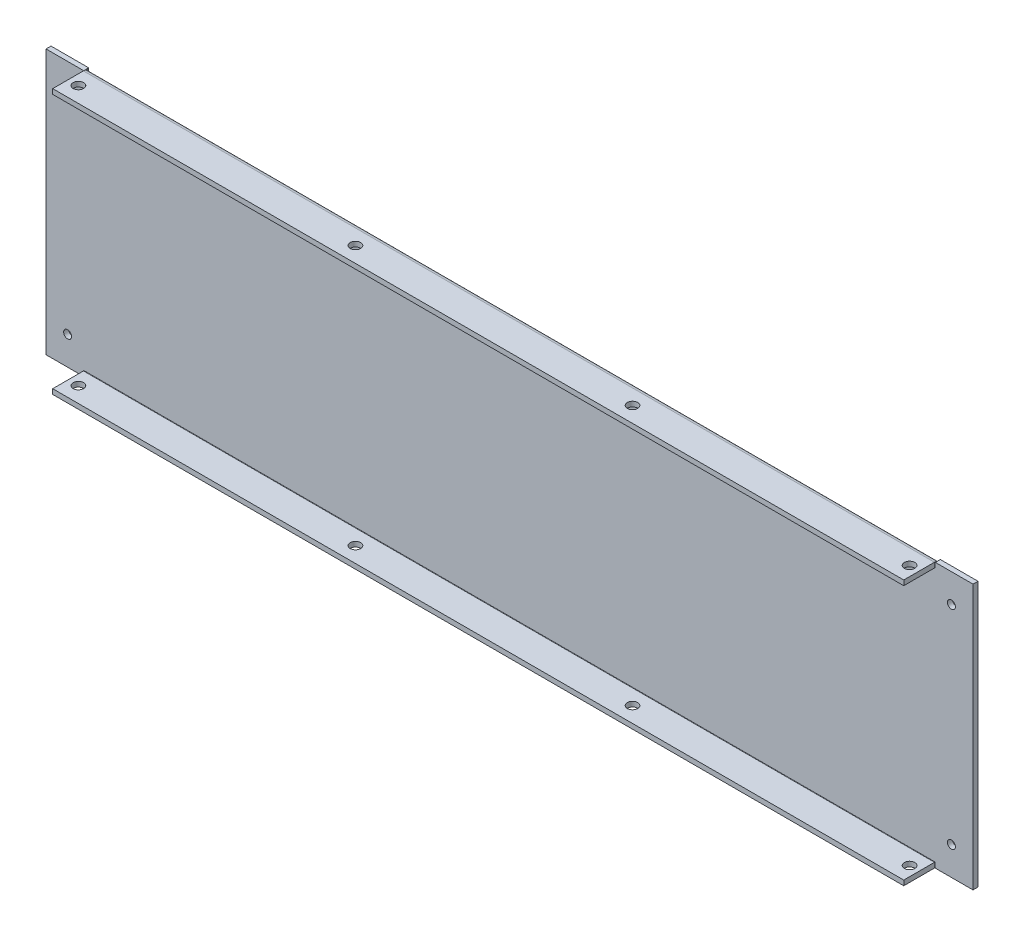
SolidWorks part; units mm, degrees
note: The reader was unsure of these and kept them because the rebuilt part matched: flange length of "Edge-Flange1".
ref_plane "Front Plane" through (0, 0, 0) normal (0, 0, 1) x (1, 0, 0)
ref_plane "Top Plane" through (0, 0, 0) normal (0, 1, 0) x (1, 0, 0)
ref_plane "Right Plane" through (0, 0, 0) normal (1, 0, 0) x (0, 0, -1)
sketch "Sketch1" plane through (0, 0, 0) normal (0, 0, 1) x (1, 0, 0)
  line L1 (0, 0) -> (424.942, 0)
  line L2 (0, 0) -> (0, 121.412)
  line L3 (0, 121.412) -> (424.942, 121.412)
  line L4 (424.942, 0) -> (424.942, 121.412)
  circle A0 centre (9.906, 13.081) radius 1.8288
  circle A1 centre (415.036, 13.081) radius 1.8288
  circle A2 centre (9.906, 108.331) radius 1.8288
  circle A3 centre (415.036, 108.331) radius 1.8288
  circle A6 centre (9.906, 203.581) radius 1.8288 [skipped]
  circle A7 centre (415.036, 203.581) radius 1.8288 [skipped]
  dimension "D3" = 9.906
  dimension "D4" = 9.906
  dimension "D5" = 3.6576
  dimension "D6" = 3.6576
  dimension "D7" = 13.081
  dimension "D8" = 13.081
  dimension "D10" = 95.25
  dimension "D11" = 121.412
  dimension "D1" = 424.942
  dimension "D2" = 121.412
  dimension "D9" = 3
sheet metal parameters "Sheet-Metal1" thickness 2.286 parameters "D1"=0.1524
base flange "Base-Flange1" sketch "Sketch1" thickness 2.286 reverse thickness direction no parameters "D1"=0.1524
sketch "Sketch4" plane through (0, 0, 0) normal (0, 0, 1) x (1, 0, 0)
  line L0 (424.942, 121.412) -> (0, 121.412) construction
  line L1 (17.272, 121.412) -> (17.2974, 121.412)
  line L2 (17.272, 121.412) -> (17.272, 121.158)
  line L3 (17.272, 121.158) -> (17.2974, 121.158)
  line L4 (17.2974, 121.412) -> (17.2974, 121.158)
  line L5 (424.942, 121.412) -> (0, 121.412) construction
  line L6 (407.416, 121.412) -> (407.416, 121.158)
  line L7 (407.67, 121.412) -> (407.67, 121.158)
  line L8 (407.416, 121.412) -> (407.67, 121.412)
  line L9 (407.416, 121.158) -> (407.67, 121.158)
  line L10 (407.416, 0.254) -> (407.416, 0)
  line L11 (407.67, 0.254) -> (407.67, 0)
  line L12 (407.416, 0.254) -> (407.67, 0.254)
  line L13 (407.416, 0) -> (407.67, 0)
  line L14 (17.272, 0.254) -> (17.272, 0)
  line L15 (17.2974, 0.254) -> (17.2974, 0)
  line L16 (17.272, 0.254) -> (17.2974, 0.254)
  line L17 (17.272, 0) -> (17.2974, 0)
  line L18 (424.942, 0) -> (424.942, 121.412) construction
  line L20 (0, 121.412) -> (0, 0) construction
  dimension "D1" = 0.254
  dimension "D2" = 0.0254
  dimension "D3" = 0.254
  dimension "D6" = 17.272
  dimension "D7" = 17.272
  dimension "D4" = 0.254
  dimension "D5" = 390.398
  dimension "D8" = 0.254
  dimension "D9" = 390.398
  dimension "D10" = 0
extrude "Cut-Extrude1" cut sketch "Sketch4" against normal blind 2.286 normal cut yes
edge flange "Edge-Flange1" sketch "Sketch7" flange profiles "Sketch7", "Sketch9" flange angle 90 flange length 16.51 flange position material inside bend radius 0.1524 thickness 2.286 relief none parameters "D6"=10, "D8"=0.254
sketch "Sketch7" plane through (0, 121.412, 0) normal (0, 1, 0) x (-1, 0, 0)
  line L0 (-407.416, 0) -> (-17.2974, 0) construction
  line L1 (-407.416, 0) -> (-17.2974, 0)
  line L2 (-407.416, 0) -> (-407.416, 14.224)
  line L3 (-407.416, 14.224) -> (-17.2974, 14.224)
  line L4 (-17.2974, 14.224) -> (-17.2974, 0)
sketch "Sketch9" plane through (0, 0, 0) normal (0, -1, 0) x (1, 0, 0)
  line L0 (17.2974, 0) -> (407.416, 0) construction
  line L1 (17.2974, 0) -> (407.416, 0)
  line L2 (17.2974, 0) -> (17.2974, 14.224)
  line L3 (17.2974, 14.224) -> (407.416, 14.224)
  line L4 (407.416, 14.224) -> (407.416, 0)
bend "EdgeBend1" bend radius 0.1524 bend angle 90 parameters "D5"=1
bend "EdgeBend2" bend radius 0.1524 bend angle 90 parameters "D5"=2
sketch "Sketch10" plane through (0, 121.412, 0) normal (0, 1, 0) x (-1, 0, 0)
  line L1 (-424.942, -2.286) -> (-424.942, 0) construction
  line L3 (-17.2974, 14.224) -> (-407.416, 14.224) construction
  circle A0 centre (-402.971, 7.112) radius 2.3876
  circle A1 centre (-275.971, 7.112) radius 2.3876
  circle A2 centre (-148.971, 7.112) radius 2.3876
  circle A3 centre (-21.971, 7.112) radius 2.3876
  dimension "D1" = 7.112
  dimension "D2" = 4.7752
  dimension "D3" = 21.971
  dimension "D4" = 4
extrude "Cut-Extrude2" cut sketch "Sketch10" against normal through all normal cut yes
flat pattern "Flat-Pattern1" [suppressed]
sketch "Bend-Lines1" plane through (0, 0, 0) normal (0, 1, 0) x (-1, 0, 0)
sketch3d "Bounding-Box1" [suppressed]
  line L0 (0, 0, 0) -> (-431.8, 0, 0) construction
  line L1 (0, 35.56, 0) -> (-431.8, 35.56, 0) construction
  line L2 (0, 0, 0) -> (0, 35.56, 0) construction
  line L3 (-431.8, 0, 0) -> (-431.8, 35.56, 0) construction
bend of the flat pattern "Flatten-<EdgeBend1>1"
bend of the flat pattern "Flatten-<EdgeBend2>1"
